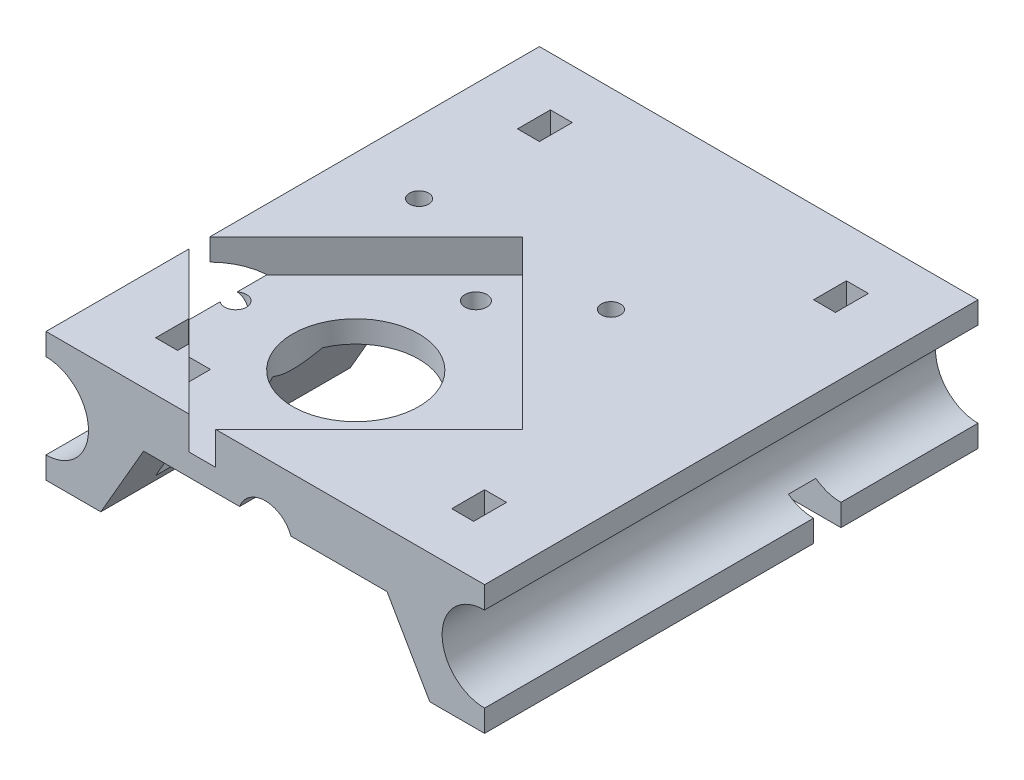
SolidWorks part; units mm, degrees
ref_plane "Plano frontal" through (0, 0, 0) normal (0, 0, 1) x (1, 0, 0)
ref_plane "Plano superior" through (0, 0, 0) normal (0, 1, 0) x (1, 0, 0)
ref_plane "Plano direito" through (0, 0, 0) normal (1, 0, 0) x (0, 0, -1)
sketch "Esboço1" plane through (0, 0, 0) normal (0, 0, 1) x (1, 0, 0)
  line L0 (40, 0) -> (-40, 0)
  line L1 (-40, -19.5) -> (-40, -23.5)
  line L2 (-40, -23.5) -> (-30, -23.5)
  line L3 (-30, -23.5) -> (-22.2058, -10)
  line L4 (-22.2058, -10) -> (-4.6837, -10)
  line L5 (-40, 0) -> (-40, -4)
  line L6 (0, 0) -> (0, -46.1263) construction
  line L7 (40, 0) -> (40, -4)
  line L8 (30, -23.5) -> (22.2058, -10)
  line L9 (40, -23.5) -> (30, -23.5)
  line L10 (40, -19.5) -> (40, -23.5)
  line L11 (4.6837, -10) -> (22.2058, -10)
  line L12 (-40, -11.75) -> (40, -11.75) construction
  arc A0 (-40, -4) -> (-40, -19.5) centre (-40, -11.75) cw
  arc A1 (40, -4) -> (40, -19.5) centre (40, -11.75) ccw
  arc A2 (4.6837, -10) -> (-4.6837, -10) centre (0, -11.75) ccw
  point P17 (0, -12.2866)
  point P21 (0, 0)
  dimension "D1" = 7.75
  dimension "D7" = 5
  dimension "D2" = 4
  dimension "D3" = 60
  dimension "D4" = 10
  dimension "D5" = 10
  dimension "D6" = 40
extrude "Ressalto-extrusão1" add sketch "Esboço1" along normal blind 90
sketch "Esboço2" plane through (0, 0, 0) normal (0, 1, 0) x (1, 0, 0)
  line L1 (-41.9056, -62) -> (-11.5, -31.5944)
  line L2 (-41.9056, -62) -> (-11.5, -92.4056)
  line L3 (-11.5, -92.4056) -> (18.9056, -62)
  line L4 (-11.5, -31.5944) -> (18.9056, -62)
  line L5 (-41.9056, -62) -> (18.9056, -62) construction
  line L6 (-11.5, -92.4056) -> (-11.5, -31.5944) construction
  line L8 (-40, -90) -> (-40, 0) construction
  line L9 (40, -90) -> (-40, -90) construction
  point P0 (-11.5, -62)
  point P9 (-41.9056, -41.5)
  dimension "D1" = 43
  dimension "D2" = 28.5
  dimension "D3" = 28
extrude "Corte-extrusão1" cut sketch "Esboço2" against normal offset from surface (6 mm away) 4 up to face at (-13.4448, -10, 45)
sketch "Esboço3" plane through (0, -6, 0) normal (0, 1, 0) x (1, 0, 0)
  line L0 (3.7028, -46.7972) -> (-26.9528, -76.9528) construction
  line L1 (-40, -63.9056) -> (-13.9056, -90) construction
  line L2 (-5.8847, -63.621) -> (3.2636, -33.545) construction
  line L3 (-17.6976, -61.875) -> (-22.0126, -34.2289) construction
  line L4 (-11.625, -39.9547) -> (10.2953, -61.875) construction
  line L5 (-11.625, -39.9547) -> (-33.5453, -61.875) construction
  line L6 (-33.5453, -61.875) -> (-11.625, -83.7953) construction
  line L7 (10.2953, -61.875) -> (-11.625, -83.7953) construction
  line L8 (-11.625, -39.9547) -> (-11.625, -83.7953) construction
  line L9 (-33.5453, -61.875) -> (10.2953, -61.875) construction
  line L11 (-11.5, -31.5944) -> (18.9056, -62) construction
  line L13 (-11.5, -31.5944) -> (-40, -60.0944) construction
  line L14 (4.6837, -90) -> (22.2058, -90) construction
  circle A0 centre (-11.625, -39.9547) radius 2
  circle A1 centre (10.2953, -61.875) radius 2
  circle A2 centre (-11.625, -83.7953) radius 2
  circle A3 centre (-33.5453, -61.875) radius 2
  circle A4 centre (-11.625, -61.875) radius 11.5
  circle A5 centre (-11.625, -61.875) radius 6 construction
  circle A6 centre (-26.9528, -35) radius 1.75
  circle A7 centre (8.0472, -35) radius 1.75
  circle A8 centre (8.0472, -35) radius 5 construction
  circle A9 centre (-26.9528, -35) radius 5 construction
  point P6 (-11.625, -61.875)
  point P21 (3.7028, -46.7972)
  point P26 (11.6921, -15)
  point P29 (-11.625, -19.9547)
  point P35 (-25.8205, -34.4231)
  point P36 (-26.9528, -34.1272)
  point P37 (0, 0)
  dimension "D1" = 4
  dimension "D3" = 23
  dimension "D4" = 12
  dimension "D5" = 3.5
  dimension "D8" = 10
  dimension "D2" = 31
  dimension "D6" = 55
  dimension "D7" = 35
extrude "Corte-extrusão2" cut sketch "Esboço3" against normal through all and the other way through all
sketch "Esboço4" plane through (0, -10, 0) normal (0, -1, 0) x (1, 0, 0)
  line L0 (-44.5112, 30) -> (44.1077, 30)
  line L2 (-44.5112, 30) -> (-44.5112, 25)
  line L3 (-44.5112, 25) -> (44.1077, 25)
  line L4 (44.1077, 25) -> (44.1077, 30)
  circle A0 centre (-26.9528, 35) radius 5 construction
  circle A1 centre (8.0472, 35) radius 5 construction
  point P11 (-23.6805, 31.2195)
  line M8 (-4.6837, 0) -> (-4.6837, 52.7061)
  dimension "D1" = 10
  dimension "D2" = 5
extrude "Corte-extrusão4" cut sketch "Esboço4" against normal blind 12 from offset 20 contours L3 L0 M8 | L2 L3 L0 | L3 L4 L0 M8 region at (-24.5975, -10, 27.5) region at (19.712, -10, 27.5)
sketch "Esboço6" plane through (0, -23.5, 0) normal (0, -1, 0) x (1, 0, 0)
  line L0 (-26.9528, 44.5) -> (-40, 44.5)
  line L1 (-40, 90) -> (-40, 30) construction
  line L2 (-26.9528, 25.5) -> (-40, 25.5)
  line L3 (-40, 60.0944) -> (-40, 0) construction
  line L5 (-40, 25.5) -> (-40, 44.5)
  arc A0 (-26.9528, 25.5) -> (-26.9528, 44.5) centre (-26.9528, 35) ccw
  dimension "D1" = 19
extrude "Corte-extrusão7" cut sketch "Esboço6" against normal up to surface (13.5 mm away) up to face at (-13.625, -10, 83.7953)
sketch "Esboço7" plane through (0, 0, 0) normal (0, 1, 0) x (1, 0, 0)
  line L0 (-32.25, 0) -> (-32.25, -90) construction
  line L1 (-13.9056, -90) -> (-40, -90) construction
  line L3 (32.25, -90) -> (32.25, 0) construction
  line L5 (27.0009, -66) -> (27.0009, -90) construction
  line L6 (40, -90) -> (-9.0944, -90) construction
  line L7 (44.8347, -45) -> (-53.0929, -45) construction
  line L8 (25.0009, -75) -> (29.0009, -75)
  line L9 (25.0009, -75) -> (25.0009, -81)
  line L10 (25.0009, -81) -> (29.0009, -81)
  line L11 (29.0009, -75) -> (29.0009, -81)
  line L12 (25.0009, -75) -> (29.0009, -81) construction
  line L13 (25.0009, -81) -> (29.0009, -75) construction
  line L14 (25.0009, -9) -> (29.0009, -15) construction
  line L15 (25.0009, -15) -> (29.0009, -9) construction
  line L16 (27.0009, -24) -> (27.0009, 0) construction
  line L17 (29.0009, -15) -> (29.0009, -9)
  line L18 (25.0009, -9) -> (29.0009, -9)
  line L19 (25.0009, -15) -> (25.0009, -9)
  line L20 (25.0009, -15) -> (29.0009, -15)
  line L21 (0, 4.9721) -> (0, -101.7412) construction
  line L22 (-27.0009, -24) -> (-27.0009, 0) construction
  line L23 (-25.0009, -15) -> (-29.0009, -9) construction
  line L24 (-25.0009, -9) -> (-29.0009, -15) construction
  line L25 (-25.0009, -81) -> (-29.0009, -75) construction
  line L26 (-25.0009, -75) -> (-29.0009, -81) construction
  line L27 (-27.0009, -66) -> (-27.0009, -90) construction
  line L28 (-25.0009, -15) -> (-29.0009, -15)
  line L29 (-25.0009, -15) -> (-25.0009, -9)
  line L30 (-25.0009, -9) -> (-29.0009, -9)
  line L31 (-29.0009, -15) -> (-29.0009, -9)
  line L32 (-29.0009, -75) -> (-29.0009, -81)
  line L33 (-25.0009, -81) -> (-29.0009, -81)
  line L34 (-25.0009, -75) -> (-25.0009, -81)
  line L35 (-25.0009, -75) -> (-29.0009, -75)
  point P10 (27.0009, -78)
  point P27 (27.0009, -12)
  point P43 (-27.0009, -12)
  point P44 (-27.0009, -78)
  dimension "D1" = 24
  dimension "D2" = 6
  dimension "D3" = 4
extrude "Corte-extrusão8" cut sketch "Esboço7" against normal through all
